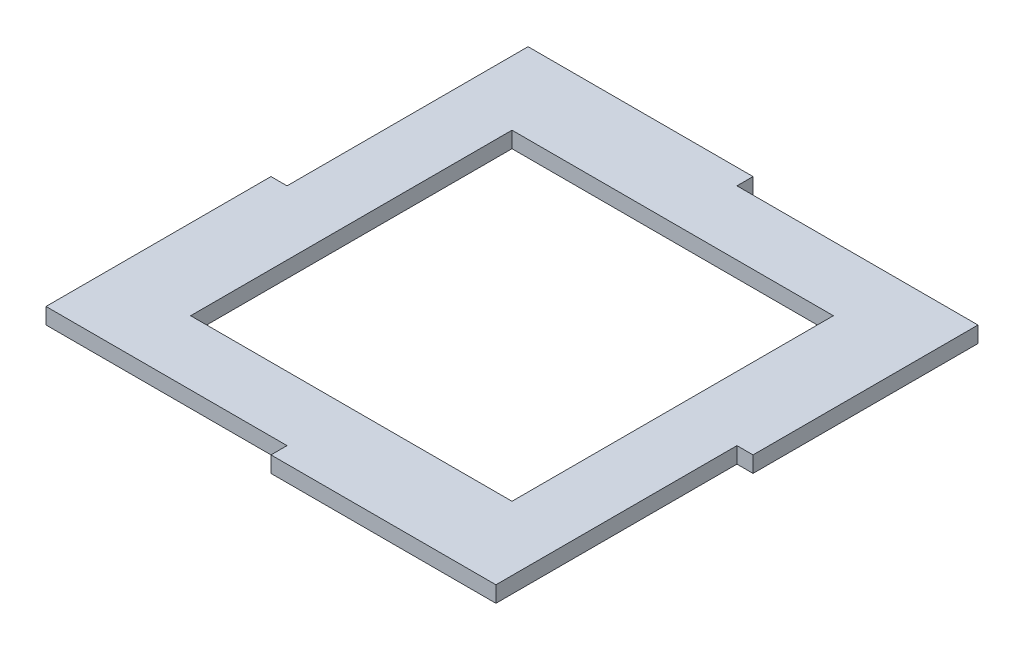
SolidWorks part; units mm, degrees
material "Acrylic (Medium-high impact)"
ref_plane "Front Plane" through (0, 0, 0) normal (0, 0, 1) x (1, 0, 0)
ref_plane "Top Plane" through (0, 0, 0) normal (0, 1, 0) x (1, 0, 0)
ref_plane "Right Plane" through (0, 0, 0) normal (1, 0, 0) x (0, 0, -1)
sketch "Sketch1" plane through (0, 0, 0) normal (0, 1, 0) x (1, 0, 0)
  line L0 (-112.5062, 93.3127) -> (-112.5062, 99.6627)
  line L1 (-112.5062, 93.3127) -> (65.2938, 93.3127)
  line L2 (-112.5062, 93.3127) -> (-112.5062, -84.4873)
  line L3 (-112.5062, -84.4873) -> (65.2938, -84.4873)
  line L4 (65.2938, 93.3127) -> (65.2938, -84.4873)
  line L5 (-112.5062, 99.6627) -> (-23.6062, 99.6627)
  line L6 (-23.6062, 99.6627) -> (-23.6062, 93.3127)
  line L7 (-112.5062, -84.4873) -> (-118.8562, -84.4873)
  line L8 (-118.8562, -84.4873) -> (-118.8562, 4.4127)
  line L9 (-118.8562, 4.4127) -> (-112.5062, 4.4127)
  line L10 (65.2938, -84.4873) -> (65.2938, -90.8373)
  line L11 (65.2938, -90.8373) -> (-23.6062, -90.8373)
  line L12 (-23.6062, -90.8373) -> (-23.6062, -84.4873)
  line L13 (65.2938, 93.3127) -> (71.6438, 93.3127)
  line L14 (71.6438, 93.3127) -> (71.6438, 4.4127)
  line L15 (71.6438, 4.4127) -> (65.2938, 4.4127)
  line L17 (39.8938, -59.0873) -> (-87.1062, -59.0873)
  line L18 (39.8938, -59.0873) -> (39.8938, 67.9127)
  line L19 (39.8938, 67.9127) -> (-87.1062, 67.9127)
  line L20 (-87.1062, -59.0873) -> (-87.1062, 67.9127)
  point P4 (-23.6062, 93.3127)
  point P5 (-112.5062, 4.4127)
  point P9 (65.2938, 4.4127)
  point P10 (-23.6062, -84.4873)
  dimension "D1" = 177.8
  dimension "D2" = 177.8
  dimension "D3" = 6.35
  dimension "D4" = 6.35
  dimension "D5" = 6.35
  dimension "D6" = 6.35
  dimension "D7" = 127
  dimension "D8" = 127
  dimension "D9" = 25.4
  dimension "D10" = 25.4
extrude "Boss-Extrude1" add sketch "Sketch1" along normal blind 6.35 contours L9 L8 L7 L2 | L6 L5 L0 L1 | L4 L1 L2 L3 | L15 L14 L13 L4 | L12 L11 L10 L3 region at (-68.0562, 0, -96.4877) region at (-68.0562, 0, -90.7982) region at (-115.6812, 0, 40.0373) region at (68.4688, 0, -48.8627) region at (20.8438, 0, 87.6623)
